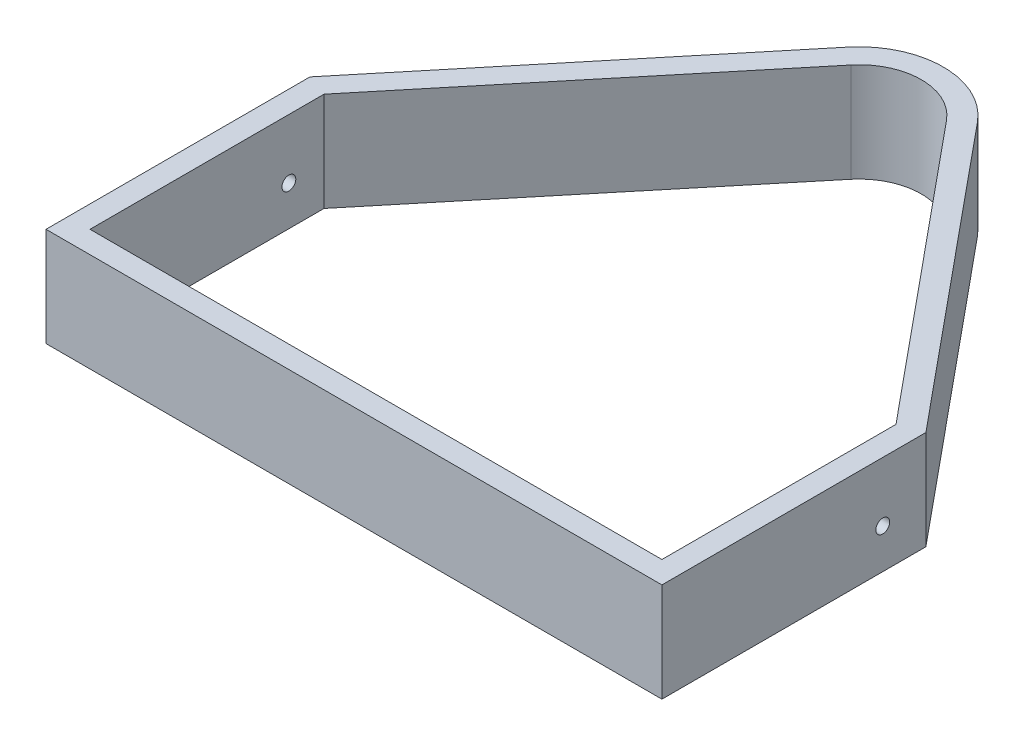
SolidWorks part; units mm, degrees
ref_plane "Front Plane" through (0, 0, 0) normal (0, 0, 1) x (1, 0, 0)
ref_plane "Top Plane" through (0, 0, 0) normal (0, 1, 0) x (1, 0, 0)
ref_plane "Right Plane" through (0, 0, 0) normal (1, 0, 0) x (0, 0, -1)
sketch "Sketch1" plane through (0, 0, 0) normal (0, 1, 0) x (1, 0, 0)
  line L0 (-88.9, 0) -> (88.9, 0)
  line L1 (-88.9, 38.1) -> (88.9, 38.1) construction
  line L2 (-88.9, 0) -> (-88.9, 76.2)
  line L3 (-88.9, 38.1) -> (0, 145.8631) construction
  line L8 (0, 145.8631) -> (88.9, 38.1) construction
  line L13 (88.9, 0) -> (88.9, 76.2)
  line L14 (-88.9, 76.2) -> (-18.7027, 161.292)
  line L15 (18.7027, 161.292) -> (88.9, 76.2)
  line L16 (-82.55, 6.35) -> (-82.55, 73.9188)
  line L17 (-82.55, 73.9188) -> (-13.8044, 157.2511)
  line L18 (13.8044, 157.2511) -> (82.55, 73.9188)
  line L19 (82.55, 6.35) -> (82.55, 73.9188)
  line L20 (-82.55, 6.35) -> (82.55, 6.35)
  arc A0 (-18.7027, 161.292) -> (18.7027, 161.292) centre (0, 145.8631) cw
  arc A2 (-13.8044, 157.2511) -> (13.8044, 157.2511) centre (0, 145.8631) cw
  point P4 (0, 0)
  dimension "D1" = 177.8
  dimension "D2" = 139.7
  dimension "D3" = 38.1
  dimension "D4" = 76.2
  dimension "D6" = 6.35
extrude "Boss-Extrude1" add sketch "Sketch1" along normal blind 28.575
sketch "Sketch2" plane through (0, 0, 0) normal (1, 0, 0) x (0, 0, -1)
  line L4 (73.9188, 28.575) -> (73.9188, 0) construction
  line L5 (0, 0) -> (76.2, 0) construction
  circle A0 centre (63.7588, 11.43) radius 10.16 construction
  circle A1 centre (63.7588, 11.43) radius 2
  dimension "D1" = 20.32
  dimension "D2" = 4
  dimension "D3" = 11.43
extrude "Cut-Extrude1" cut sketch "Sketch2" against normal up to next from surface starting at face at (-82.55, 14.2875, -40.1344)
extrude "Cut-Extrude3" cut sketch "Sketch2<2>" along normal up to next from surface starting at face at (82.55, 14.2875, -40.1344)
sketch "Sketch2<2>" plane through (0, 0, 0) normal (1, 0, 0) x (0, 0, -1) same geometry as "Sketch2"
